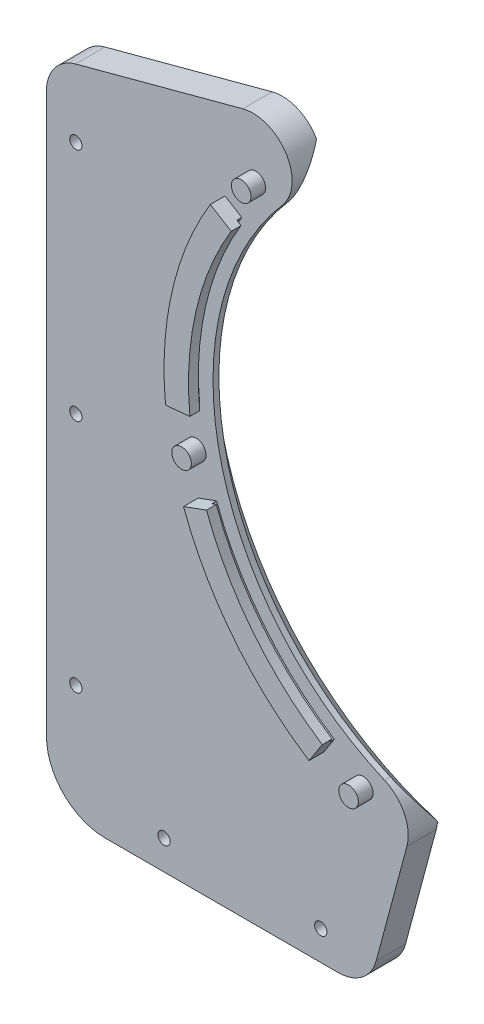
SolidWorks part; units mm, degrees
ref_plane "Front Plane" through (0, 0, 0) normal (0, 0, 1) x (1, 0, 0)
ref_plane "Top Plane" through (0, 0, 0) normal (0, 1, 0) x (1, 0, 0)
ref_plane "Right Plane" through (0, 0, 0) normal (1, 0, 0) x (0, 0, -1)
other "Configuration Table"
sketch "Sketch1" plane through (0, 0, 0) normal (0, 0, 1) x (1, 0, 0)
  line L3 (0, 0) -> (0, 95.25) construction
  line L4 (0, -106.7771) -> (0, 106.7771) construction
  line L5 (0, 0) -> (74.4694, 59.3874) construction
  line L6 (0, 0) -> (92.8619, -21.1951) construction
  line L7 (0, 0) -> (41.3274, -85.8173) construction
  line L8 (0, 0) -> (-41.3274, -85.8173) construction
  line L9 (0, 0) -> (-92.8619, -21.1951) construction
  line L10 (0, 0) -> (-74.4694, 59.3874) construction
  line L11 (-88.1918, 53.5711) -> (-82.7647, 50.2744)
  line L13 (-96.3816, -9.3854) -> (-102.7017, -10.0009)
  line L14 (-90.909, -33.3624) -> (-96.8703, -35.5502)
  line L15 (-56.2145, -86.5309) -> (-52.7551, -81.2059)
  circle A0 centre (0, 0) radius 95.25 construction
  circle A1 centre (-78.1929, 62.3568) radius 3.175
  circle A2 centre (-78.1929, 62.3568) radius 4.7625 construction
  circle A3 centre (-97.505, -22.2549) radius 3.175
  circle A4 centre (-97.505, -22.2549) radius 4.7625 construction
  circle A5 centre (-43.3938, -90.1081) radius 3.175
  circle A6 centre (-43.3938, -90.1081) radius 4.7625 construction
  circle A7 centre (0, 0) radius 96.8375 construction
  arc A8 (-82.7647, 50.2744) -> (-96.3816, -9.3854) centre (0, 0) ccw
  arc A9 (-88.1918, 53.5711) -> (-102.7017, -10.0009) centre (0, 0) ccw
  arc A10 (-56.2145, -86.5309) -> (-96.8703, -35.5502) centre (0, 0) cw
  arc A11 (-52.7551, -81.2059) -> (-90.909, -33.3624) centre (0, 0) cw
  point P23 (0, 0)
  dimension "D1" = 190.5
  dimension "D2" = 9.525
  dimension "D3" = 6.35
  dimension "D4" = 7
  dimension "D5" = 6.35
  dimension "D6" = 12.7
  dimension "D7" = 12.7
extrude "Boss-Extrude1" add sketch "Sketch1" along normal blind 4.7625
sketch "Sketch2" plane through (0, 0, 0) normal (0, 0, 1) x (1, 0, 0)
  line L0 (0, 0) -> (-41.3274, -85.8173) construction
  line L1 (0, 0) -> (-92.8619, -21.1951) construction
  line L2 (0, 0) -> (-74.4694, 59.3874) construction
  line L3 (0, 0) -> (-41.3274, -85.8173) construction
  line L4 (0, 0) -> (-92.8619, -21.1951) construction
  line L5 (0, 0) -> (-74.4694, 59.3874) construction
  line L6 (-82.4301, 80.9271) -> (-136.637, 66.4024)
  line L7 (127, 127) -> (-127, 127) construction
  line L8 (127, 127) -> (127, -127) construction
  line L9 (127, -127) -> (-127, -127) construction
  line L10 (-127, 127) -> (-127, -127) construction
  line L11 (127, 127) -> (-127, -127) construction
  line L12 (127, -127) -> (-127, 127) construction
  line L13 (-146.05, 54.1351) -> (-146.05, -127)
  line L14 (-127, -146.05) -> (-51.4696, -146.05)
  line L15 (-39.2023, -136.637) -> (-29.2478, -99.4863)
  line L16 (-127, 44.45) -> (-146.05, 44.45) construction
  line L17 (-107.95, -127) -> (-107.95, -146.05) construction
  line L18 (-136.525, 44.45) -> (-136.525, -107.95) construction
  circle A0 centre (0, 0) radius 95.25 construction
  circle A1 centre (0, 0) radius 95.25 construction
  arc A2 (-69.55, 60.3374) -> (-36.4829, -84.5388) centre (0, 0) ccw
  arc A3 (-36.4829, -84.5388) -> (-29.2478, -99.4863) centre (-41.5151, -96.1993) cw
  arc A4 (-69.55, 60.3374) -> (-82.4301, 80.9271) centre (-79.1431, 68.6598) ccw
  arc A5 (-136.637, 66.4024) -> (-146.05, 54.1351) centre (-133.35, 54.1351) ccw
  arc A6 (-146.05, -127) -> (-127, -146.05) centre (-127, -127) ccw
  arc A7 (-51.4696, -146.05) -> (-39.2023, -136.637) centre (-51.4696, -133.35) ccw
  circle A8 centre (-136.525, 44.45) radius 1.9844
  circle A9 centre (-136.525, -31.75) radius 1.9844
  circle A10 centre (-136.525, -107.95) radius 1.9844
  circle A11 centre (-57.15, -136.525) radius 1.9844
  circle A12 centre (-107.95, -136.525) radius 1.9844
  point P38 (-136.525, 44.45)
  point P39 (-107.95, -136.525)
  point P42 (-136.525, -31.75)
  dimension "D1" = 92.075
  dimension "D9" = 12.7
  dimension "D10" = 3.9688
  dimension "D2" = 127
  dimension "D3" = 254
  dimension "D4" = 19.05
  dimension "D5" = 75
  dimension "D6" = 75
  dimension "D7" = 3.81
  dimension "D8" = 3.81
  dimension "D11" = 19.05
  dimension "D12" = 50.8
  dimension "D13" = 19.05
  dimension "D14" = 152.4
extrude "Boss-Extrude2" add sketch "Sketch2" against normal blind 9.525
sketch "Sketch3" plane through (0, 0, 4.7625) normal (0, 0, 1) x (1, 0, 0)
  line L2 (-82.7647, 50.2744) -> (-88.1918, 53.5711) construction
  line L3 (-102.7017, -10.0009) -> (-96.3816, -9.3854) construction
  line L6 (-81.4079, 49.4502) -> (-88.1918, 53.5711)
  line L7 (-102.7017, -10.0009) -> (-94.8016, -9.2316)
  line L8 (0, 0) -> (-92.8619, -21.1951) construction
  line L9 (0, 0) -> (-92.8619, -21.1951) construction
  line L10 (-96.8703, -35.5502) -> (-89.4187, -32.8155)
  line L11 (-51.8903, -79.8746) -> (-56.2145, -86.5309)
  arc A2 (-82.7647, 50.2744) -> (-96.3816, -9.3854) centre (0, 0) ccw construction
  arc A3 (-88.1918, 53.5711) -> (-102.7017, -10.0009) centre (0, 0) ccw construction
  arc A6 (-82.7647, 50.2744) -> (-96.3816, -9.3854) centre (0, 0) ccw construction
  arc A7 (-88.1918, 53.5711) -> (-102.7017, -10.0009) centre (0, 0) ccw
  arc A8 (-81.4079, 49.4502) -> (-94.8016, -9.2316) centre (0, 0) ccw
  arc A9 (-52.7551, -81.2059) -> (-90.909, -33.3624) centre (0, 0) cw construction
  arc A10 (-51.8903, -79.8746) -> (-89.4187, -32.8155) centre (0, 0) cw
  arc A11 (-56.2145, -86.5309) -> (-96.8703, -35.5502) centre (0, 0) cw
  dimension "D1" = 1.5875
extrude "Boss-Extrude3" add sketch "Sketch3" against normal blind 3.175
chamfer "Chamfer1" distance 7.62 angle 50 1 edges at (-89.7665, -20.4886, -9.525) tangent propagation no first distance on face at (-71.3915, -16.2946, -4.7625)
